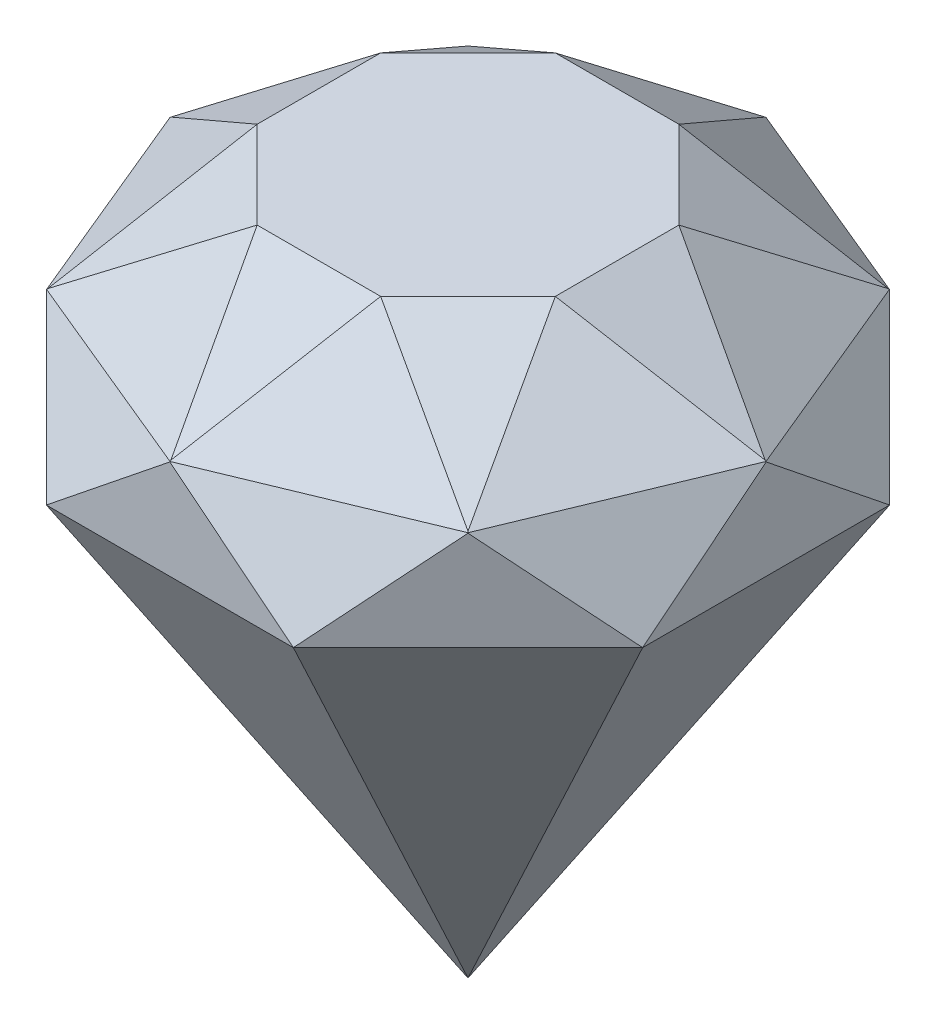
SolidWorks part; units mm, degrees
material "1345 Alloy"
ref_plane "Front Plane" through (0, 0, 0) normal (0, 0, 1) x (1, 0, 0)
ref_plane "Top Plane" through (0, 0, 0) normal (0, 1, 0) x (1, 0, 0)
ref_plane "Right Plane" through (0, 0, 0) normal (1, 0, 0) x (0, 0, -1)
sketch "Sketch1" plane through (0, 0, 0) normal (0, 1, 0) x (1, 0, 0)
  line L0 (0, 0) -> (-12.4264, 30)
  line L1 (0, 0) -> (12.4264, 30)
  line L2 (12.4264, 30) -> (-12.4264, 30)
  line L3 (0, 0) -> (0, 30) construction
  dimension "D1" = 45
  dimension "D2" = 30
extrude "Boss-Extrude1" add sketch "Sketch1" along normal blind 70
sketch "Sketch2" plane through (0, 0, 0) normal (1, 0, 0) x (0, 0, -1)
  line L0 (15, 70) -> (30, 60)
  line L1 (0, 70) -> (30, 70) construction
  line L2 (30, 70) -> (30, 0) construction
  line L3 (30, 70) -> (30, 60)
  line L4 (30, 50) -> (0, 0)
  line L5 (0, 0) -> (30, 0)
  line L6 (30, 50) -> (30, 0)
  line L7 (30, 70) -> (15, 70)
  dimension "D1" = 15
  dimension "D2" = 10
  dimension "D3" = 10
extrude "Cut-Extrude1" cut sketch "Sketch2" against normal through all both and the other way through all
ref_axis "Axis1" through (0, -3.5, 0) along (0, 1, 0)
pattern_circular "CirPattern1" count 8 every 45 about axis through (0, -3.5, 0) along (0, 1, 0) of "Boss-Extrude1", "Cut-Extrude1"
ref_plane "Plane1" through (0, 0, 0) normal (0.9239, 0, -0.3827) x (0, 1, 0)
sketch "Sketch3" plane through (0, 0, 0) normal (0.9239, 0, -0.3827) x (0, 1, 0)
  line L4 (70, 32.4718) -> (70, 16.2359)
  line L9 (70, 16.2359) -> (60, 27.7)
  line L10 (60, 27.7) -> (50, 32.4718)
  line L11 (50, 32.4718) -> (70, 32.4718)
  line L12 (70, 11.4805) -> (70, 16.2359) construction
  line L13 (60, 32.4718) -> (50, 32.4718) construction
  line L15 (-3.5, 0) -> (73.5, 0) construction
  dimension "D1" = 27.7
  dimension "D2" = 10
extrude "Cut-Extrude2" cut sketch "Sketch3" against normal through all both and the other way through all contours L4 region at (10.5134, 64.1987, 25.3815)
pattern_circular "CirPattern2" count 8 every 45 about axis through (0, -3.5, 0) along (0, 1, 0) of "Cut-Extrude2"
